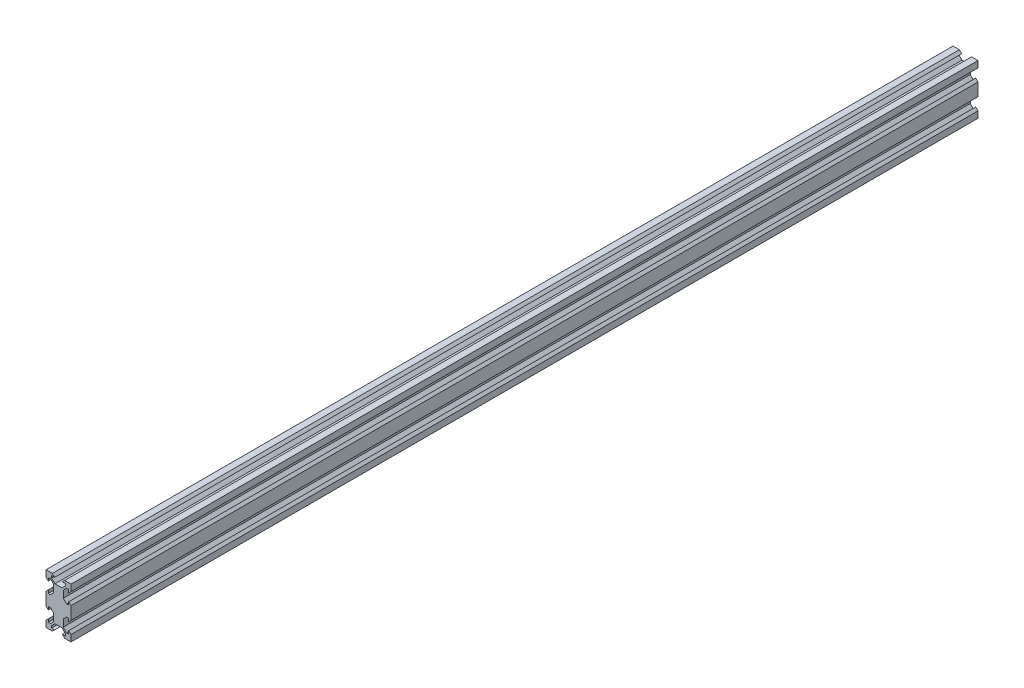
SolidWorks part; units mm, degrees
ref_plane "Front Plane" through (0, 0, 0) normal (0, 0, 1) x (1, 0, 0)
ref_plane "Top Plane" through (0, 0, 0) normal (0, 1, 0) x (1, 0, 0)
ref_plane "Right Plane" through (0, 0, 0) normal (1, 0, 0) x (0, 0, -1)
sketch "Sketch1" plane through (0, 0, 0) normal (0, 0, 1) x (1, 0, 0)
  line L1 (0, 0) -> (20, 0)
  line L2 (0, 0) -> (0, 40)
  line L3 (0, 40) -> (20, 40)
  line L4 (20, 0) -> (20, 40)
  line L5 (0, 0) -> (20, 40) construction
  line L6 (0, 40) -> (20, 0) construction
  point P4 (10, 20)
  dimension "D1" = 20
  dimension "D2" = 40
extrude "Boss-Extrude1" add sketch "Sketch1" along normal blind 725
sketch "Sketch2" plane through (0, 0, 725) normal (0, 0, 1) x (1, 0, 0)
  line L0 (5.12, 40) -> (6.94, 38.18)
  line L1 (20, 40) -> (0, 40) construction
  line L3 (13.06, 38.18) -> (14.88, 40)
  line L4 (0, 40) -> (20, 40) construction
  line L5 (20, 40) -> (10, 40) construction
  line L6 (10, 40) -> (10, 38.18) construction
  line L7 (5.12, 40) -> (14.88, 40)
  line L8 (6.94, 38.18) -> (4.5, 38.18)
  line L9 (4.5, 38.18) -> (4.5, 36.4758)
  line L10 (4.5, 36.4758) -> (7.1658, 33.81)
  line L11 (7.1658, 33.81) -> (12.8342, 33.81)
  line L12 (12.8342, 33.81) -> (15.5, 36.4758)
  line L13 (15.5, 36.4758) -> (15.5, 38.18)
  line L14 (15.5, 38.18) -> (13.06, 38.18)
  line L15 (20, 40) -> (0, 20) construction
  line L16 (0, 40) -> (0, 0) construction
  line L17 (20, 30) -> (18.18, 30) construction
  line L18 (18.18, 35.5) -> (18.18, 33.06)
  line L19 (16.4758, 35.5) -> (18.18, 35.5)
  line L20 (13.81, 32.8342) -> (16.4758, 35.5)
  line L21 (13.81, 27.1658) -> (13.81, 32.8342)
  line L22 (16.4758, 24.5) -> (13.81, 27.1658)
  line L23 (18.18, 24.5) -> (16.4758, 24.5)
  line L24 (18.18, 26.94) -> (18.18, 24.5)
  line L25 (20, 25.12) -> (20, 34.88)
  line L26 (18.18, 33.06) -> (20, 34.88)
  line L28 (20, 25.12) -> (18.18, 26.94)
  line L29 (0, 20) -> (20, 20) construction
  line L30 (20, 0) -> (20, 40) construction
  line L31 (20, 10) -> (18.18, 10) construction
  line L32 (10, 0) -> (10, 1.82) construction
  line L33 (20, 0) -> (10, 0) construction
  line L34 (20, 14.88) -> (18.18, 13.06)
  line L36 (18.18, 6.94) -> (20, 5.12)
  line L37 (20, 14.88) -> (20, 5.12)
  line L38 (18.18, 13.06) -> (18.18, 15.5)
  line L39 (18.18, 15.5) -> (16.4758, 15.5)
  line L40 (16.4758, 15.5) -> (13.81, 12.8342)
  line L41 (13.81, 12.8342) -> (13.81, 7.1658)
  line L42 (13.81, 7.1658) -> (16.4758, 4.5)
  line L43 (16.4758, 4.5) -> (18.18, 4.5)
  line L44 (18.18, 4.5) -> (18.18, 6.94)
  line L45 (15.5, 1.82) -> (13.06, 1.82)
  line L46 (15.5, 3.5242) -> (15.5, 1.82)
  line L47 (12.8342, 6.19) -> (15.5, 3.5242)
  line L48 (7.1658, 6.19) -> (12.8342, 6.19)
  line L49 (4.5, 3.5242) -> (7.1658, 6.19)
  line L50 (4.5, 1.82) -> (4.5, 3.5242)
  line L51 (6.94, 1.82) -> (4.5, 1.82)
  line L52 (5.12, 0) -> (14.88, 0)
  line L53 (13.06, 1.82) -> (14.88, 0)
  line L55 (5.12, 0) -> (6.94, 1.82)
  line L56 (10, 40) -> (10, 0) construction
  line L57 (0, 10) -> (1.82, 10) construction
  line L58 (0, 30) -> (1.82, 30) construction
  line L59 (1.82, 4.5) -> (1.82, 6.94)
  line L60 (3.5242, 4.5) -> (1.82, 4.5)
  line L61 (6.19, 7.1658) -> (3.5242, 4.5)
  line L62 (6.19, 12.8342) -> (6.19, 7.1658)
  line L63 (3.5242, 15.5) -> (6.19, 12.8342)
  line L64 (1.82, 15.5) -> (3.5242, 15.5)
  line L65 (1.82, 13.06) -> (1.82, 15.5)
  line L66 (0, 14.88) -> (0, 5.12)
  line L67 (1.82, 6.94) -> (0, 5.12)
  line L69 (0, 14.88) -> (1.82, 13.06)
  line L70 (0, 25.12) -> (1.82, 26.94)
  line L72 (1.82, 33.06) -> (0, 34.88)
  line L73 (0, 25.12) -> (0, 34.88)
  line L74 (1.82, 26.94) -> (1.82, 24.5)
  line L75 (1.82, 24.5) -> (3.5242, 24.5)
  line L76 (3.5242, 24.5) -> (6.19, 27.1658)
  line L77 (6.19, 27.1658) -> (6.19, 32.8342)
  line L78 (6.19, 32.8342) -> (3.5242, 35.5)
  line L79 (3.5242, 35.5) -> (1.82, 35.5)
  line L80 (1.82, 35.5) -> (1.82, 33.06)
  dimension "D1" = 90
  dimension "D3" = 6.12
  dimension "D5" = 11
  dimension "D6" = 6.19
  dimension "D7" = 1.38
extrude "Cut-Extrude1" cut sketch "Sketch2" against normal through all
